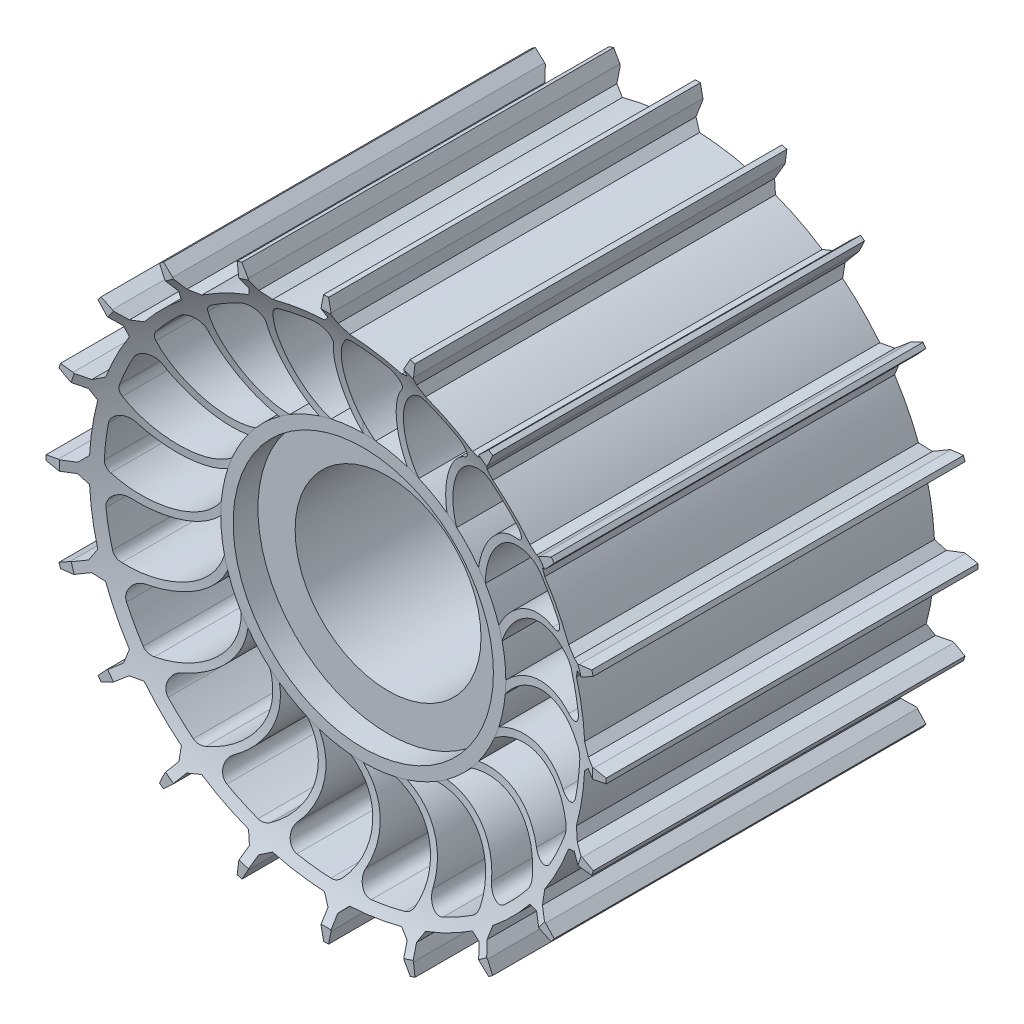
SolidWorks part; units mm, degrees
note: The reader was unsure of these and kept them because the rebuilt part matched: shared geometry of "Sketch2<3>".
ref_plane "Front Plane" through (0, 0, 0) normal (0, 0, 1) x (1, 0, 0)
ref_plane "Top Plane" through (0, 0, 0) normal (0, 1, 0) x (1, 0, 0)
ref_plane "Right Plane" through (0, 0, 0) normal (1, 0, 0) x (0, 0, -1)
sketch "Sketch1" plane through (0, 0, 0) normal (0, 0, 1) x (1, 0, 0)
  circle A0 centre (0, 0) radius 96
  circle A1 centre (0, 0) radius 100
  dimension "D1" = 4
  dimension "D2" = 200
extrude "Boss-Extrude1" add sketch "Sketch1" along normal mid plane 150
sketch "Sketch2" plane through (0, 0, 0) normal (0, 0, 1) x (1, 0, 0)
  line L0 (0, 0) -> (0, 98) construction
  line L1 (-2, 113) -> (2, 113)
  line L2 (-2, 113) -> (-2, 98)
  line L3 (-2, 98) -> (2, 98)
  line L4 (2, 113) -> (2, 98)
  line L5 (0, 98) -> (4.6767, 98)
  circle A1 centre (0, 0) radius 57.5 construction
  arc A2 (0, 98) -> (0, 57.5) centre (19.3375, 77.75) ccw
  arc A3 (4.9799, 57.284) -> (4.6767, 98) centre (19.3375, 77.75) cw
  arc A4 (4.9799, 57.284) -> (0, 57.5) centre (0, 0) ccw
  dimension "D4" = 115
  dimension "D5" = 3
  dimension "D6" = 25
  dimension "D1" = 15
  dimension "D2" = 4
  dimension "D3" = 98
extrude "Boss-Extrude2" add sketch "Sketch2" along normal mid plane 150 contours L4 L3 L2 L1
chamfer "Chamfer1" distance 3 angle 45 2 edges at (2, 99.98, 0) (-2, 99.98, 0)
chamfer "Chamfer2" distance 5 distance2 1 2 edges at (-2, 113, 0) (2, 113, 0)
pattern_circular "CirPattern1" count 20 over 360 about axis through (0, 0, 0) along (0, 0, 1) of "Boss-Extrude2", "Chamfer1", "Chamfer2"
extrude "Boss-Extrude3" add sketch "Sketch2<3>" along normal mid plane 150 contours A4 A3 L5 L3 A2
sketch "Sketch2<3>" plane through (0, 0, 0) normal (0, 0, 1) x (1, 0, 0) same geometry as "Sketch2"
fillet "Fillet1" radius 5 2 edges at (2.2238, 95.9742, 0) (-1.9142, 95.9809, 0)
pattern_circular "CirPattern3" count 20 over 360 about axis through (0, 0, 0) along (0, 0, 1) of "Boss-Extrude3", "Fillet1"
sketch "Sketch3" plane through (0, 0, 0) normal (1, 0, 0) x (0, 0, -1)
  line L0 (0, 0) -> (-75, 0) construction
  line L1 (-75, 0) -> (-75, 107.5) construction
  line L2 (-75, 57.5) -> (-60, 57.5)
  line L5 (-75, 107.5) -> (-75, 57.5)
  line L6 (-60, 57.5) -> (-60, 107.5) construction
  line L7 (0, 0) -> (0, 113) construction
  line L8 (-75, 113) -> (75, 113) construction
  line L9 (75, 57.5) -> (60, 57.5)
  line L10 (75, 107.5) -> (75, 57.5)
  arc A1 (-60, 57.5) -> (-75, 107.5) centre (-150.8333, 57.5) ccw
  arc A2 (60, 57.5) -> (75, 107.5) centre (150.8333, 57.5) cw
  dimension "D1" = 57.5
  dimension "D2" = 15
  dimension "D3" = 50
revolve "Cut-Revolve1" cut sketch "Sketch3" angle 360 about L0
sketch "Sketch4" plane through (0, 0, 0) normal (0, 0, 1) x (1, 0, 0)
  circle A0 centre (0, 0) radius 57.5
  circle A2 centre (0, 0) radius 37.5
  dimension "D1" = 20
extrude "Boss-Extrude4" add sketch "Sketch4" along normal mid plane 120
sketch "Sketch5" plane through (0, 0, 60) normal (0, 0, 1) x (1, 0, 0)
  circle A0 centre (0, 0) radius 52.5
  arc A1 (0, 57.5) -> (-12.9656, 56.0191) centre (0, 0) ccw construction
  dimension "D1" = 5
extrude "Cut-Extrude1" cut sketch "Sketch5" against normal blind 10
mirror "Mirror1" about plane through (0, 0, 0) normal (0, 0, 1) of "Cut-Extrude1"
